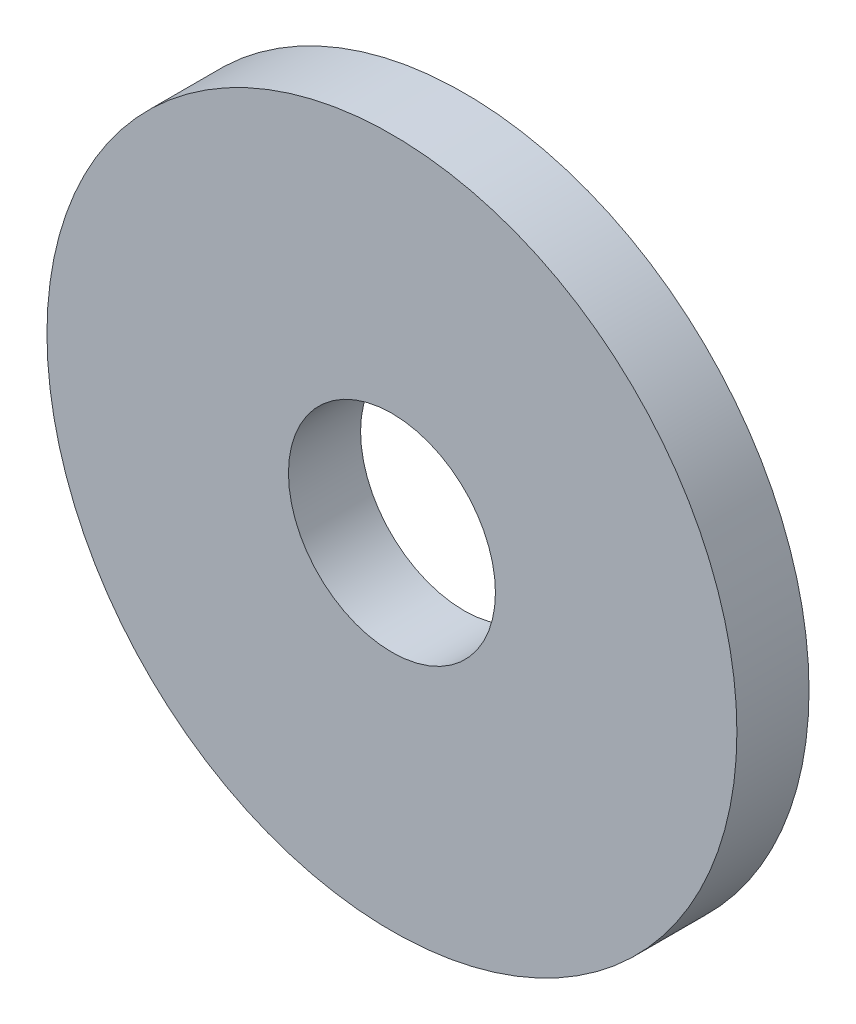
SolidWorks part; units mm, degrees
material "Cast Stainless Steel"
ref_plane "Front Plane" through (0, 0, 0) normal (0, 0, 1) x (1, 0, 0)
ref_plane "Top Plane" through (0, 0, 0) normal (0, 1, 0) x (1, 0, 0)
ref_plane "Right Plane" through (0, 0, 0) normal (1, 0, 0) x (0, 0, -1)
sketch "Sketch1" plane through (0, 0, 0) normal (0, 0, 1) x (1, 0, 0)
  circle A0 centre (0, 0) radius 11
  circle A1 centre (0, 0) radius 3.3
  dimension "OD" = 22
  dimension "ID1" = 6.6
extrude "Boss-Extrude1" add sketch "Sketch1" along normal blind 2.3
ref_axis "Center Axis 1" through (0, 0, 2.3) along (0, 0, -1)
ref_plane "Contact Plane 1" through (0, 0, 2.3) normal (0, 0, 1) x (1, 0, 0)
ref_plane "Contact Plane 2" through (0, 0, 0) normal (0, 0, -1) x (-1, 0, 0)
move or copy body "Body-Move/Copy1" [suppressed] bodies to move or copy 101
